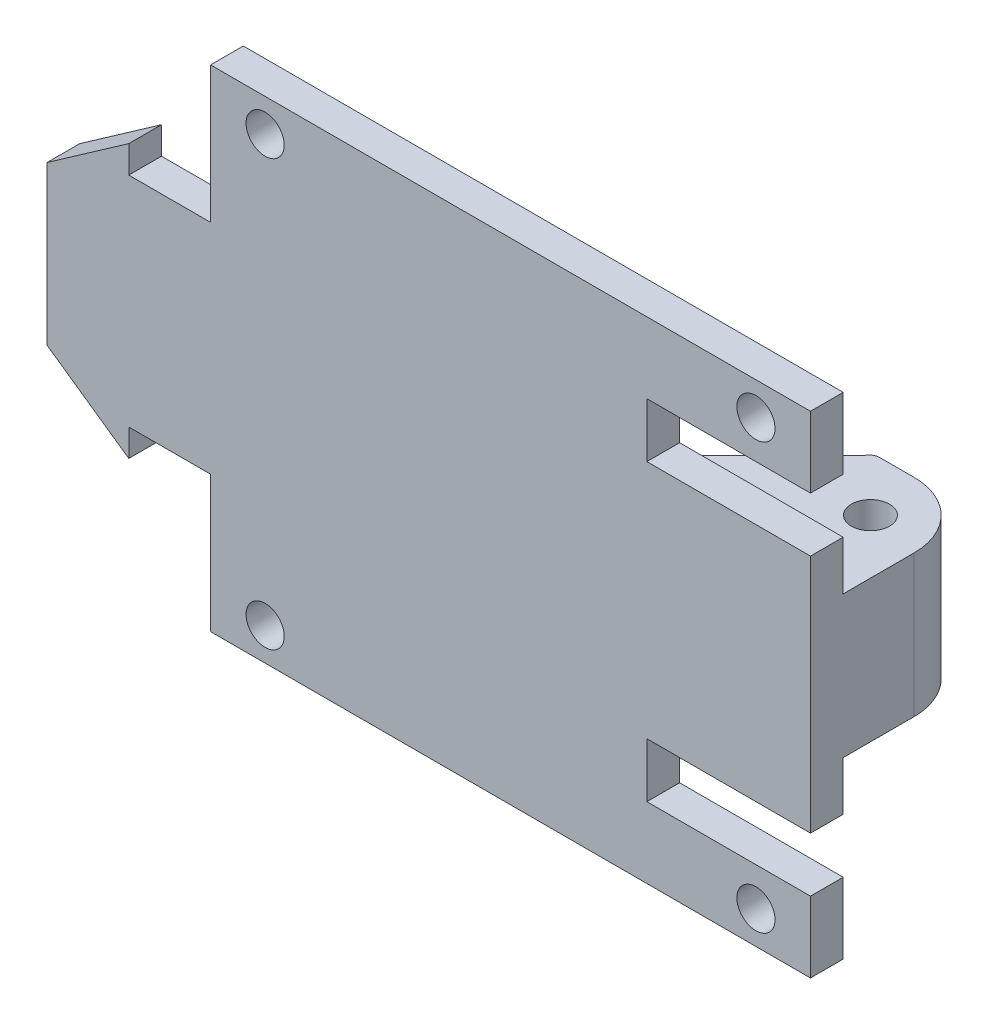
SolidWorks part; units mm, degrees
ref_plane "Front Plane" through (0, 0, 0) normal (0, 0, 1) x (1, 0, 0)
ref_plane "Top Plane" through (0, 0, 0) normal (0, 1, 0) x (1, 0, 0)
ref_plane "Right Plane" through (0, 0, 0) normal (1, 0, 0) x (0, 0, -1)
sketch "Sketch1" plane through (0, 0, 0) normal (0, 0, 1) x (1, 0, 0)
  line L0 (10.563, 19.3432) -> (10.563, -25.6568)
  line L1 (-44.437, 19.3432) -> (10.563, 19.3432)
  line L2 (-44.437, 19.3432) -> (-44.437, -25.6568)
  line L3 (-44.437, -25.6568) -> (10.563, -25.6568)
extrude "Boss-Extrude1" add sketch "Sketch1" along normal blind 3
sketch "Sketch2" plane through (0, 0, 0) normal (0, 0, -1) x (-1, 0, 0)
  line L0 (44.437, 19.3432) -> (44.437, -25.6568) construction
  line L5 (-0.563, -9.6568) -> (-10.563, -9.6568)
  line L6 (-0.563, -9.6568) -> (-0.563, 3.3432)
  line L7 (-0.563, 3.3432) -> (-10.563, 3.3432)
  line L8 (-10.563, -9.6568) -> (-10.563, 3.3432)
  line L10 (-20.563, -3.1568) -> (44.437, -3.1568) construction
  point P4 (44.437, -3.1568)
  dimension "D1" = 13
  dimension "D2" = 10
  dimension "D3" = 6.5
extrude "Boss-Extrude2" add sketch "Sketch2" along normal blind 12.5
sketch "Sketch3" plane through (0, 3.3432, 0) normal (0, 1, 0) x (1, 0, 0)
  line L0 (0.563, 2.5) -> (10.563, 2.5) construction
  line L2 (0.563, 12.5) -> (0.563, 0) construction
  line L3 (10.563, 12.5) -> (10.563, 0) construction
  line L4 (0.563, 2.5) -> (10.563, 12.5) construction
  line L5 (0.563, 12.5) -> (10.563, 2.5) construction
  line L6 (0.563, 0) -> (10.563, 0) construction
  circle A0 centre (5.563, 7.5) radius 1.75
  dimension "D1" = 2.5
extrude "Cut-Extrude1" cut sketch "Sketch3" against normal blind 13.5
sketch "Sketch4" plane through (0, 0, 0) normal (0, 0, -1) x (-1, 0, 0)
  line L0 (-0.563, -9.6568) -> (-0.563, 3.3432) construction
  line L1 (4.437, 7.8432) -> (-15.563, 7.8432)
  line L2 (4.437, 7.8432) -> (4.437, 12.8432)
  line L3 (4.437, 12.8432) -> (-15.563, 12.8432)
  line L4 (-15.563, 7.8432) -> (-15.563, 12.8432)
  line L6 (-0.563, 3.3432) -> (-10.563, 3.3432) construction
  dimension "D1" = 20
  dimension "D2" = 5
  dimension "D3" = 5
  dimension "D4" = 4.5
fillet "Fillet1" radius 6 1 edges at (10.563, -3.1568, -12.5)
chamfer "Chamfer1" distance 12 angle 45 1 edges at (0.563, -3.1568, 0)
fillet "Fillet3" radius 1 1 edges at (0.563, -3.1568, -12.5)
ref_plane "Plane1" through (0, -3.1568, 0) normal (0, 1, 0) x (1, 0, 0)
ref_axis "Axis1" through (5.563, -9.6568, -7.5) along (0, 1, 0)
ref_plane "Plane3" through (5.563, 0, 0) normal (1, 0, 0) x (0, 0, -1)
sketch "Sketch6" plane through (5.563, 0, 0) normal (1, 0, 0) x (0, 0, -1)
  line L0 (12.5, 3.3432) -> (6.5, 3.3432) construction
  line L1 (7.5, 12.8432) -> (18, 12.8432)
  line L2 (7.5, 12.8432) -> (7.5, 7.8432)
  line L3 (7.5, 7.8432) -> (18, 7.8432)
  line L4 (18, 12.8432) -> (18, 7.8432)
  line L5 (7.5, -9.6568) -> (7.5, 3.3432) construction
  dimension "D1" = 4.5
  dimension "D2" = 5
  dimension "D3" = 10.5
  dimension "D4" = 0
extrude "Cut-Extrude3" cut sketch "Sketch4" against normal blind 5
mirror "Mirror2" about plane through (0, -3.1568, 0) normal (0, 1, 0) of "Cut-Extrude3"
sketch "Sketch7" plane through (0, 0, 0) normal (0, 0, -1) x (-1, 0, 0)
  line L0 (-5.563, -3.1568) -> (48.7662, -3.1568) construction
  line L1 (6.875, -3.1568) -> (-6.875, -3.1568) construction
  line L2 (-5.563, 3.575) -> (-5.563, -3.575) construction
  line L3 (-5.563, -3.1568) -> (-29.9947, -3.1568) construction
  line L4 (-5.563, -3.1568) -> (-5.563, 24.1217) construction
  line L5 (-5.563, -3.1568) -> (-5.563, -32.3324) construction
  line L6 (-5.563, -9.6568) -> (-5.563, 3.3432) construction
  line L7 (39.437, 24.1217) -> (39.437, -29.7158) construction
  line L8 (44.437, 19.3432) -> (44.437, -25.6568) construction
  line L9 (48.7662, 16.3432) -> (-29.9947, 16.3432) construction
  line L10 (-29.9947, -22.6568) -> (53.7379, -22.6568) construction
  line L11 (44.437, -25.6568) -> (-10.563, -25.6568) construction
  line L12 (-10.563, 19.3432) -> (44.437, 19.3432) construction
  circle A2 centre (-5.563, 16.3432) radius 1.75
  circle A3 centre (39.437, 16.3432) radius 1.75
  circle A5 centre (39.437, -22.6568) radius 1.75
  circle A6 centre (-5.563, -22.6568) radius 1.75
  dimension "D1" = 5
  dimension "D5" = 3.5
  dimension "D6" = 3.5
  dimension "D2" = 3
  dimension "D3" = 3
extrude "Cut-Extrude4" cut sketch "Sketch7" against normal blind 5
sketch "Sketch8" plane through (0, 0, 0) normal (0, 0, -1) x (-1, 0, 0)
  line L0 (44.437, 19.3432) -> (44.437, -25.6568) construction
  line L1 (44.437, 9.3432) -> (59.437, 9.3432) construction
  line L2 (44.437, 9.3432) -> (44.437, -15.6568) construction
  line L3 (44.437, -15.6568) -> (59.437, -15.6568) construction
  line L4 (59.437, 9.3432) -> (59.437, -15.6568) construction
  line L5 (-10.563, 19.3432) -> (44.437, 19.3432) construction
  line L6 (44.437, -25.6568) -> (-10.563, -25.6568) construction
  line L7 (51.937, 9.3432) -> (51.937, -15.6568) construction
  line L8 (44.437, 6.8432) -> (51.937, 6.8432)
  line L9 (44.437, -13.1568) -> (51.937, -13.1568)
  line L10 (51.937, -15.6568) -> (59.437, -10.4053)
  line L11 (51.937, 9.3432) -> (59.437, 4.0916)
  line L12 (44.437, 6.8432) -> (44.437, -13.1568)
  line L13 (51.937, 9.3432) -> (51.937, 6.8432)
  line L14 (51.937, -13.1568) -> (51.937, -15.6568)
  line L15 (59.437, 4.0916) -> (59.437, -10.4053)
  dimension "D1" = 10
  dimension "D2" = 10
  dimension "D3" = 15
  dimension "D4" = 2.5
  dimension "D5" = 2.5
  dimension "D6" = 55
  dimension "D7" = 55
extrude "Boss-Extrude4" add sketch "Sketch8" against normal blind 3 contours L11 L15 L10 L14 L9 L12 L8 L13
